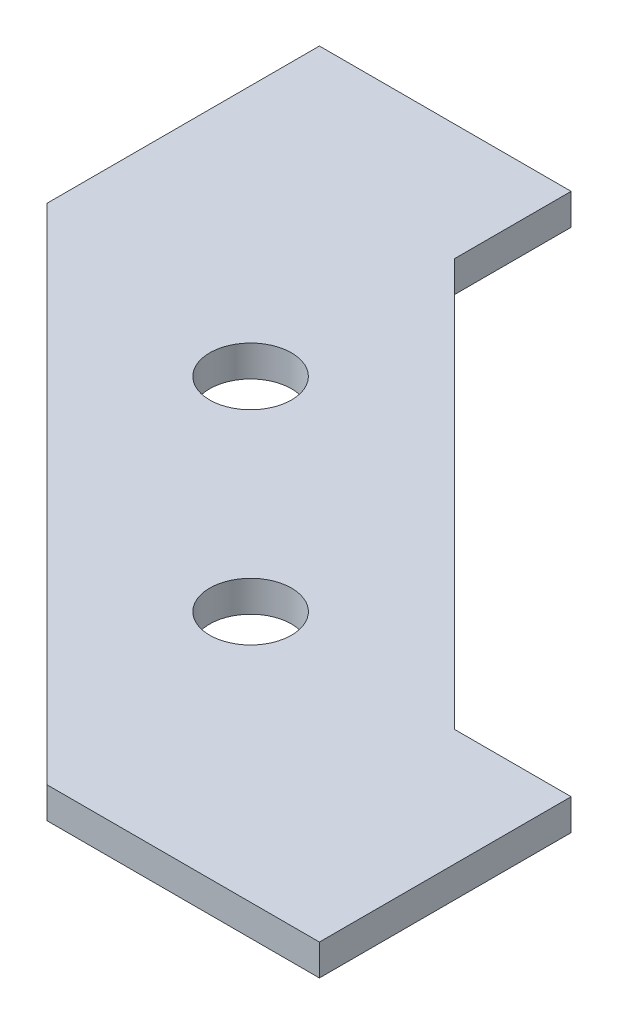
SolidWorks part; units mm, degrees
material "AISI 1020"
ref_plane "Спереди" through (0, 0, 0) normal (0, 0, 1) x (1, 0, 0)
ref_plane "Сверху" through (0, 0, 0) normal (0, 1, 0) x (1, 0, 0)
ref_plane "Справа" through (0, 0, 0) normal (1, 0, 0) x (0, 0, -1)
sketch "Эскиз1" plane through (0, 0, 0) normal (0, 1, 0) x (1, 0, 0)
  line L0 (-13.0815, 13.0815) -> (13.0815, -13.0815) construction
  line L1 (-1000, 0) -> (49000, 0) construction
  line L2 (-50.213, -50.213) -> (35305.1261, 35305.1261) construction
  line L3 (39.2444, -13.0815) -> (-13.0815, 39.2444)
  line L4 (-13.0815, 39.2444) -> (-13.0815, 54.2444)
  line L5 (-13.0815, 54.2444) -> (-45.4074, 54.2444)
  line L6 (-45.4074, 54.2444) -> (-45.4074, 19.2444)
  line L7 (-45.4074, 19.2444) -> (19.2444, -45.4074)
  line L8 (39.2444, -13.0815) -> (54.2444, -13.0815)
  line L9 (54.2444, -13.0815) -> (54.2444, -45.4074)
  line L10 (54.2444, -45.4074) -> (19.2444, -45.4074)
  circle A0 centre (-13.0815, 13.0815) radius 13.5 construction
  circle A1 centre (13.0815, -13.0815) radius 13.5 construction
  circle A2 centre (-13.0815, 13.0815) radius 5.25
  circle A3 centre (13.0815, -13.0815) radius 5.25
  point P5 (0, 0)
  point P18 (13.0815, 13.0815)
  point P22 (-13.0815, -13.0815)
  dimension "D1" = 27
  dimension "D3" = 10
  dimension "D7" = 10.5
  dimension "D2" = 45
  dimension "D4" = 15
  dimension "D5" = 35
  dimension "D6" = 5
base flange "Базовая кромка1" sketch "Эскиз1" thickness 4 reverse thickness direction no parameters "D1"=0.75
sketch "Сгиб-Линии1" [suppressed] plane through (0, 0, 0) normal (0, 1, 0) x (1, 0, 0)
sketch "Граничная рамка1" [suppressed] plane through (0, 0, 0) normal (0, 1, 0) x (1, 0, 0)
sheet metal parameters "Листовой металл3" thickness 4 parameters "D1"=0.75
flat pattern "Развертка3" [suppressed]
sketch "Сгиб-Линии2" plane through (0, 0, 0) normal (0, 1, 0) x (1, 0, 0)
sketch3d "Граничная рамка2" [suppressed]
  line L0 (70.4074, -29.2444, 0) -> (-29.2444, 70.4074, 0) construction
  line L1 (36.7444, -62.9074, 0) -> (-62.9074, 36.7444, 0) construction
  line L2 (70.4074, -29.2444, 0) -> (36.7444, -62.9074, 0) construction
  line L3 (-29.2444, 70.4074, 0) -> (-62.9074, 36.7444, 0) construction
